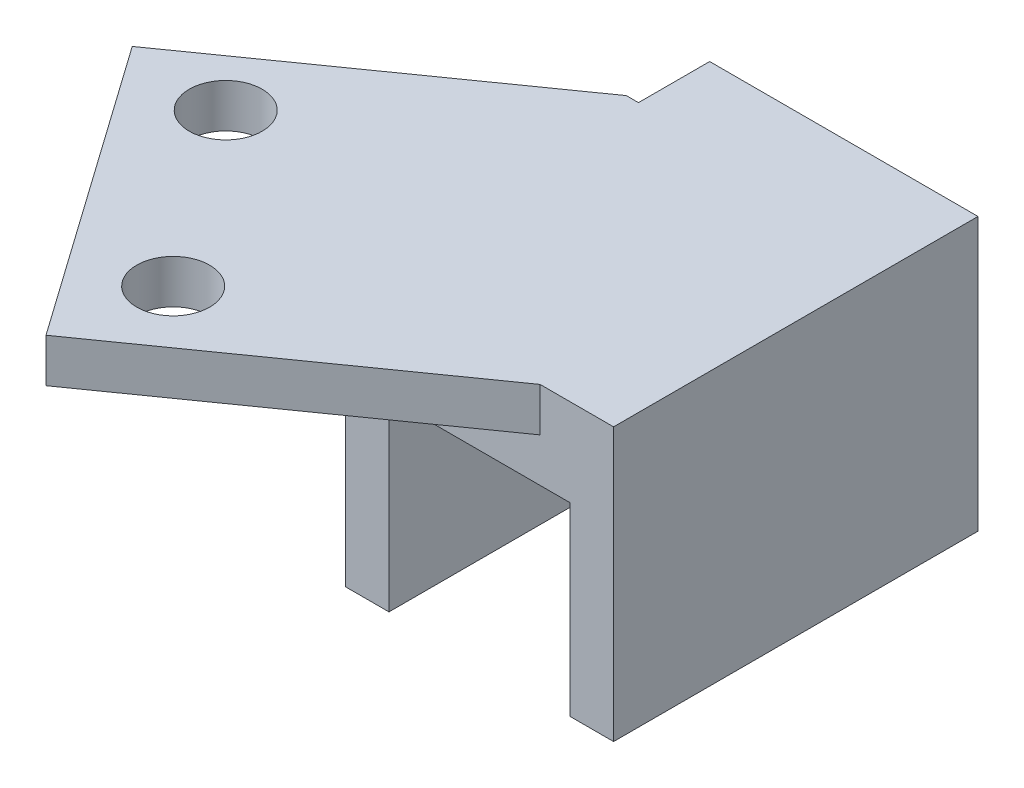
SolidWorks part; units mm, degrees
ref_plane "Front Plane" through (0, 0, 0) normal (0, 0, 1) x (1, 0, 0)
ref_plane "Top Plane" through (0, 0, 0) normal (0, 1, 0) x (1, 0, 0)
ref_plane "Right Plane" through (0, 0, 0) normal (1, 0, 0) x (0, 0, -1)
sketch "Sketch1" plane through (0, 0, 0) normal (0, 0, 1) x (1, 0, 0)
  line L0 (-18.408, -12.7) -> (-18.408, 18.7)
  line L5 (-12.408, 12.7) -> (12.408, -12.7) construction
  line L6 (-12.408, -12.7) -> (12.408, 12.7) construction
  line L11 (-18.408, 18.7) -> (18.408, 18.7)
  line L12 (18.408, -12.7) -> (18.408, 18.7)
  line L13 (-12.408, -12.7) -> (12.408, -12.7)
  line L14 (-12.408, -12.7) -> (-12.408, 12.7)
  line L15 (-12.408, 12.7) -> (12.408, 12.7)
  line L16 (12.408, -12.7) -> (12.408, 12.7)
  line L17 (-12.408, -12.7) -> (12.408, 12.7) construction
  line L18 (-12.408, 12.7) -> (12.408, -12.7) construction
  line L19 (-18.408, -12.7) -> (-12.408, -12.7)
  line L20 (12.408, -12.7) -> (18.408, -12.7)
  line L22 (-12.408, -12.7) -> (-18.408, -12.7)
  line L23 (-12.408, -12.7) -> (-12.408, 18.7)
  line L24 (-12.408, 18.7) -> (-18.408, 18.7)
  line L25 (-18.408, -12.7) -> (-18.408, 18.7)
  line L26 (-12.408, 18.7) -> (18.408, 18.7)
  line L27 (-12.408, 18.7) -> (-12.408, 12.7)
  line L28 (-12.408, 12.7) -> (18.408, 12.7)
  line L29 (18.408, 18.7) -> (18.408, 12.7)
  line L30 (18.408, -12.7) -> (12.408, -12.7)
  line L31 (18.408, -12.7) -> (18.408, 12.7)
  line L32 (18.408, 12.7) -> (12.408, 12.7)
  line L33 (12.408, -12.7) -> (12.408, 12.7)
  point P0 (0, 0)
  point P6 (0, 29.5014)
  point P11 (0, 0)
  dimension "D1" = 25.4
  dimension "D2" = 6
extrude "Boss-Extrude1" add sketch "Sketch1" along normal blind 50 contours L15 L28 L12 L11 L23 | L28 L16 L20 L12 | L23 L22 L25 L24 region at (3, 15.7, 0) region at (15.408, 0, 0)
sketch "Sketch3" plane through (0, 18.7, 0) normal (0, 1, 0) x (1, 0, 0)
  line L0 (0, -25) -> (0, 0) construction
  line L1 (-18.408, -50) -> (18.408, -50) construction
  line L2 (18.408, -25) -> (-18.408, -25) construction
  line L3 (18.408, -50) -> (18.408, 0) construction
  line L4 (-18.408, -50) -> (-18.408, 0) construction
  line L5 (0, -25) -> (-28.5713, -45.1683) construction
  line L6 (-28.5713, -45.1683) -> (-58.3376, -66.1801) construction
  line L7 (-45.8245, -38.9865) -> (-28.5238, -63.4954) construction
  line L8 (8.3223, -50) -> (-18.408, -10.7099) construction
  line L9 (8.3223, -50) -> (-31.4166, -78.0514) construction
  line L10 (8.3223, -50) -> (-31.4166, -78.0514)
  line L11 (8.3223, -50) -> (-20.0774, -9.7676)
  line L12 (-31.4166, -78.0514) -> (-59.8164, -37.819)
  line L13 (-20.0774, -9.7676) -> (-59.8164, -37.819)
  line L14 (-20.0774, -9.7676) -> (0, -9.7676)
  line L15 (0, -9.7676) -> (8.3223, -50)
  circle A0 centre (-28.5238, -63.4954) radius 5
  circle A1 centre (-45.8245, -38.9865) radius 5
  point P14 (0, -12.5)
  point P17 (-14.2857, -35.0842)
  point P21 (-37.1741, -51.241)
  point P22 (-28.5713, -45.1683)
  line M13 (18.408, 0) -> (-18.408, 0)
  line M14 (-18.408, 0) -> (-18.408, -50)
  line M15 (-18.408, -50) -> (18.408, -50)
  line M16 (18.408, -50) -> (18.408, 0)
  dimension "D1" = 30
  dimension "D2" = 10
  dimension "D3" = 10
extrude "Boss-Extrude2" add sketch "Sketch3" along normal blind 6 contours M16 | L11 L13 L12 L10 A1 A0 M15 M14 | L11 M15 M14 | L15 L14 L11 M14 | L14 L11 M14 | L14 L15 M15 M16 M13 M14 region at (-9.4979, 18.7, 37.3775) region at (-3.8445, 18.7, 23.2404) region at (-29.4582, 18.7, 45.1531) region at (6.8097, 18.7, 19.0425) region at (-18.9645, 18.7, 10.5559)
